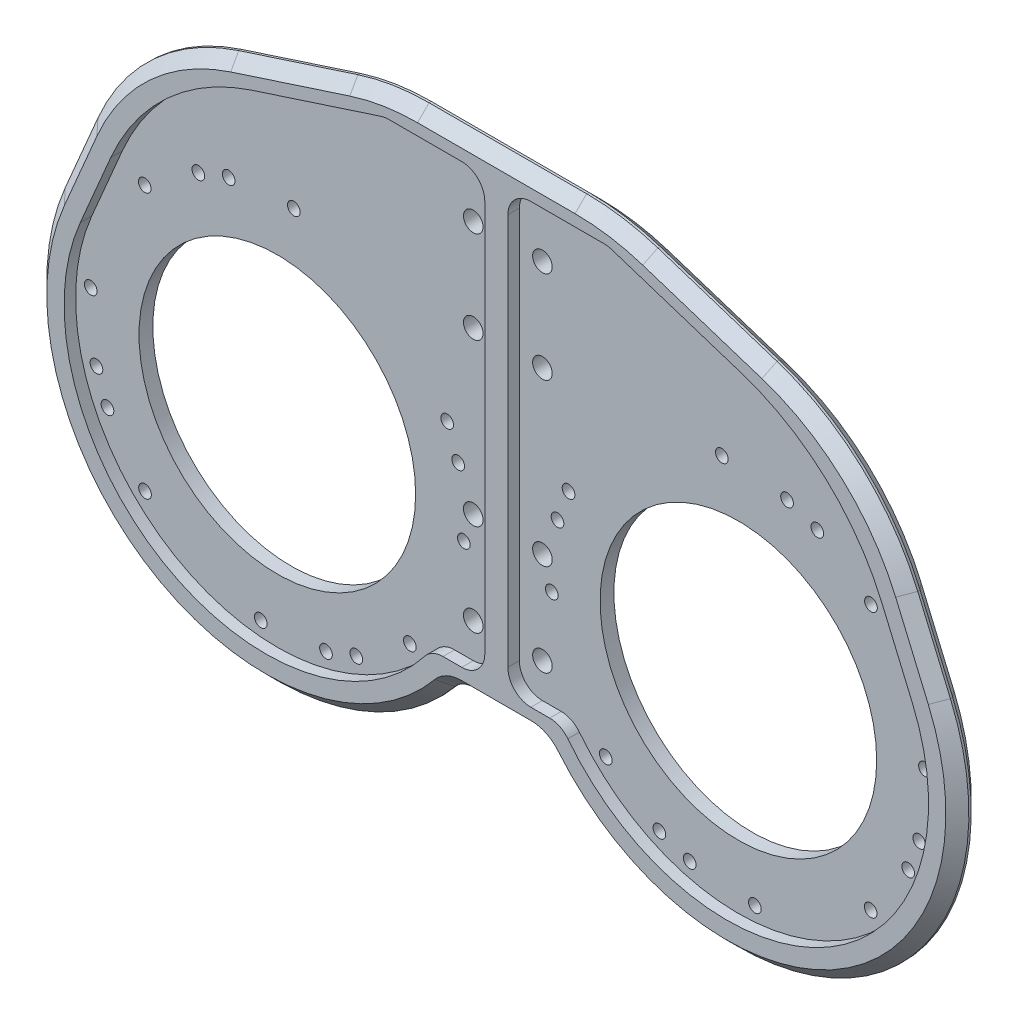
SolidWorks part; units mm, degrees
material "6061 合金"
ref_plane "前视基准面" through (0, 0, 0) normal (0, 0, 1) x (1, 0, 0)
ref_plane "上视基准面" through (0, 0, 0) normal (0, 1, 0) x (1, 0, 0)
ref_plane "右视基准面" through (0, 0, 0) normal (1, 0, 0) x (0, 0, -1)
other "Configuration Table"
sketch "草图1" plane through (0, 0, 0) normal (0, 0, 1) x (1, 0, 0)
  line L0 (0, 0) -> (0, 250) construction
  line L1 (0, 250) -> (769.4209, 0)
  line L3 (769.4209, 0) -> (0, 0)
  line L4 (-50, 352.899) -> (-50, -139.8009) construction
  line L5 (-869.4209, 0) -> (-100, 0)
  line L6 (-100, 250) -> (-869.4209, 0)
  line L7 (-100, 0) -> (-100, 250) construction
  line L8 (-100, 250) -> (0, 250)
  line L9 (0, 0) -> (-100, 0)
  circle A0 centre (50, 100) radius 85 construction
  circle A1 centre (50, 100) radius 60
  circle A2 centre (-150, 100) radius 85 construction
  circle A3 centre (-150, 100) radius 60
  dimension "D1" = 170
  dimension "D4" = 120
  dimension "D2" = 100
  dimension "D3" = 72
  dimension "D5" = 250
  dimension "D6" = 100
  dimension "D7" = 50
extrude "凸台-拉伸1" add sketch "草图1" along normal blind 6 contours L9 L3 L1 L8 L6 L5 A1 A3 region at (-50, 86.7466, 0)
sketch "草图4" plane through (0, 0, 6) normal (0, 0, 1) x (1, 0, 0)
  line L0 (-50, 330.4726) -> (-50, -61.6586) construction
  arc A0 (259.7806, 158.4465) -> (255.249, 156.3335) centre (257.5148, 157.39) ccw construction
  arc A1 (278.6673, 106.1128) -> (283.1989, 108.2258) centre (280.9331, 107.1693) ccw construction
  arc A2 (276.1928, 77.8292) -> (280.7244, 79.9423) centre (278.4586, 78.8857) ccw construction
  arc A3 (271.409, 64.6857) -> (275.9405, 66.7988) centre (273.6748, 65.7423) ccw construction
  arc A4 (255.1242, 41.4287) -> (259.6558, 43.5418) centre (257.39, 42.4852) ccw construction
  arc A5 (204.9035, 18.0104) -> (209.4351, 20.1235) centre (207.1693, 19.0669) ccw construction
  arc A6 (176.62, 20.4849) -> (181.1515, 22.598) centre (178.8857, 21.5414) ccw construction
  arc A7 (163.4765, 25.2687) -> (168.008, 27.3818) centre (165.7423, 26.3252) ccw construction
  arc A8 (140.2194, 41.5535) -> (144.751, 43.6665) centre (142.4852, 42.61) ccw construction
  arc A9 (121.3327, 93.8872) -> (116.8011, 91.7742) centre (119.0669, 92.8307) ccw construction
  arc A10 (123.8072, 122.1708) -> (119.2756, 120.0577) centre (121.5414, 121.1143) ccw construction
  arc A11 (128.591, 135.3143) -> (124.0595, 133.2012) centre (126.3252, 134.2577) ccw construction
  arc A12 (144.8758, 158.5713) -> (140.3442, 156.4582) centre (142.61, 157.5148) ccw construction
  arc A13 (195.0965, 181.9896) -> (190.5649, 179.8765) centre (192.8307, 180.9331) ccw construction
  arc A14 (223.38, 179.5151) -> (218.8485, 177.402) centre (221.1143, 178.4586) ccw construction
  arc A15 (236.5235, 174.7313) -> (231.992, 172.6182) centre (234.2577, 173.6748) ccw construction
  arc A16 (259.7806, 158.4465) -> (255.249, 156.3335) centre (257.5148, 157.39) ccw construction
  arc A17 (278.6673, 106.1128) -> (283.1989, 108.2258) centre (280.9331, 107.1693) ccw construction
  arc A18 (276.1928, 77.8292) -> (280.7244, 79.9423) centre (278.4586, 78.8857) ccw construction
  arc A19 (271.409, 64.6857) -> (275.9405, 66.7988) centre (273.6748, 65.7423) ccw construction
  arc A20 (255.1242, 41.4287) -> (259.6558, 43.5418) centre (257.39, 42.4852) ccw construction
  arc A21 (204.9035, 18.0104) -> (209.4351, 20.1235) centre (207.1693, 19.0669) ccw construction
  arc A22 (176.62, 20.4849) -> (181.1515, 22.598) centre (178.8857, 21.5414) ccw construction
  arc A23 (163.4765, 25.2687) -> (168.008, 27.3818) centre (165.7423, 26.3252) ccw construction
  arc A24 (140.2194, 41.5535) -> (144.751, 43.6665) centre (142.4852, 42.61) ccw construction
  arc A25 (121.3327, 93.8872) -> (116.8011, 91.7742) centre (119.0669, 92.8307) ccw construction
  arc A26 (123.8072, 122.1708) -> (119.2756, 120.0577) centre (121.5414, 121.1143) ccw construction
  arc A27 (128.591, 135.3143) -> (124.0595, 133.2012) centre (126.3252, 134.2577) ccw construction
  arc A28 (144.8758, 158.5713) -> (140.3442, 156.4582) centre (142.61, 157.5148) ccw construction
  arc A29 (195.0965, 181.9896) -> (190.5649, 179.8765) centre (192.8307, 180.9331) ccw construction
  arc A30 (223.38, 179.5151) -> (218.8485, 177.402) centre (221.1143, 178.4586) ccw construction
  arc A31 (236.5235, 174.7313) -> (231.992, 172.6182) centre (234.2577, 173.6748) ccw construction
  circle A32 centre (257.5148, 157.39) radius 2.75
  circle A33 centre (234.2577, 173.6748) radius 2.75
  circle A34 centre (221.1143, 178.4586) radius 2.75
  circle A35 centre (192.8307, 180.9331) radius 2.75
  circle A36 centre (142.61, 157.5148) radius 2.75
  circle A37 centre (126.3252, 134.2577) radius 2.75
  circle A38 centre (121.5414, 121.1143) radius 2.75
  circle A39 centre (119.0669, 92.8307) radius 2.75
  circle A40 centre (142.4852, 42.61) radius 2.75
  circle A41 centre (165.7423, 26.3252) radius 2.75
  circle A42 centre (178.8857, 21.5414) radius 2.75
  circle A43 centre (207.1693, 19.0669) radius 2.75
  circle A44 centre (257.39, 42.4852) radius 2.75
  circle A45 centre (273.6748, 65.7423) radius 2.75
  circle A46 centre (278.4586, 78.8857) radius 2.75
  circle A47 centre (280.9331, 107.1693) radius 2.75
  circle A48 centre (50, 100) radius 60 construction
  circle A49 centre (-150, 100) radius 60 construction
  arc A50 (-336.5235, 174.7313) -> (-331.992, 172.6182) centre (-334.2577, 173.6748) cw construction
  arc A51 (-323.38, 179.5151) -> (-318.8485, 177.402) centre (-321.1143, 178.4586) cw construction
  arc A52 (-295.0965, 181.9896) -> (-290.5649, 179.8765) centre (-292.8307, 180.9331) cw construction
  arc A53 (-244.8758, 158.5713) -> (-240.3442, 156.4582) centre (-242.61, 157.5148) cw construction
  arc A54 (-228.591, 135.3143) -> (-224.0595, 133.2012) centre (-226.3252, 134.2577) cw construction
  arc A55 (-223.8072, 122.1708) -> (-219.2756, 120.0577) centre (-221.5414, 121.1143) cw construction
  arc A56 (-221.3327, 93.8872) -> (-216.8011, 91.7742) centre (-219.0669, 92.8307) cw construction
  arc A57 (-240.2194, 41.5535) -> (-244.751, 43.6665) centre (-242.4852, 42.61) cw construction
  arc A58 (-263.4765, 25.2687) -> (-268.008, 27.3818) centre (-265.7423, 26.3252) cw construction
  arc A59 (-276.62, 20.4849) -> (-281.1515, 22.598) centre (-278.8857, 21.5414) cw construction
  arc A60 (-304.9035, 18.0104) -> (-309.4351, 20.1235) centre (-307.1693, 19.0669) cw construction
  arc A61 (-355.1242, 41.4287) -> (-359.6558, 43.5418) centre (-357.39, 42.4852) cw construction
  arc A62 (-371.409, 64.6857) -> (-375.9405, 66.7988) centre (-373.6748, 65.7423) cw construction
  arc A63 (-376.1928, 77.8292) -> (-380.7244, 79.9423) centre (-378.4586, 78.8857) cw construction
  arc A64 (-378.6673, 106.1128) -> (-383.1989, 108.2258) centre (-380.9331, 107.1693) cw construction
  arc A65 (-359.7806, 158.4465) -> (-355.249, 156.3335) centre (-357.5148, 157.39) cw construction
  circle A66 centre (-380.9331, 107.1693) radius 2.75
  circle A67 centre (-378.4586, 78.8857) radius 2.75
  circle A68 centre (-373.6748, 65.7423) radius 2.75
  circle A69 centre (-357.39, 42.4852) radius 2.75
  circle A70 centre (-307.1693, 19.0669) radius 2.75
  circle A71 centre (-278.8857, 21.5414) radius 2.75
  circle A72 centre (-265.7423, 26.3252) radius 2.75
  circle A73 centre (-242.4852, 42.61) radius 2.75
  circle A74 centre (-219.0669, 92.8307) radius 2.75
  circle A75 centre (-221.5414, 121.1143) radius 2.75
  circle A76 centre (-226.3252, 134.2577) radius 2.75
  circle A77 centre (-242.61, 157.5148) radius 2.75
  circle A78 centre (-292.8307, 180.9331) radius 2.75
  circle A79 centre (-321.1143, 178.4586) radius 2.75
  circle A80 centre (-334.2577, 173.6748) radius 2.75
  circle A81 centre (-357.5148, 157.39) radius 2.75
  dimension "D1" = 5.5
extrude "切除-拉伸2" [suppressed] cut sketch "草图4" against normal blind 10 contours A44 | A45 | A46 | A47 | A32 | A33 | A34 | A35 | A36 | A37 | A38 | A39 | A40 | A41 | A42 | A73 | A72 | A71 | A70 | A69 | A68 | A67 | A66 | A81 | A80 | A79 | A78 | A77 | A76 | A75 | A74 | A43
sketch "草图5" plane through (0, 0, 0) normal (0, 0, -1) x (-1, 0, 0)
  line L0 (50, 354.5789) -> (50, -118.9875) construction
  circle A16 centre (150, 100) radius 60 construction
  circle A17 centre (-50, 100) radius 60 construction
extrude "切除-拉伸3" [suppressed] cut sketch "草图5" against normal blind 5.5
fillet "圆角1" radius 100 2 edges at (-869.4209, 0, 3) (769.4209, 0, 3)
sketch "草图6" plane through (0, 0, 6) normal (0, 0, 1) x (1, 0, 0)
  line L0 (-50, 293.5967) -> (-50, -68.7433) construction
  line L1 (-70, 40) -> (-30, 40)
  line L2 (138.0457, 0) -> (-238.0457, 0) construction
  line L3 (50, 0) -> (-150, 0)
  circle A0 centre (50, 100) radius 85.25 construction
  arc A1 (-30, 40) -> (50, 0) centre (50, 100) ccw
  circle A2 centre (50, 100) radius 60 construction
  circle A3 centre (-150, 100) radius 60 construction
  arc A4 (-70, 40) -> (-150, 0) centre (-150, 100) cw
  dimension "D1" = 170.5
  dimension "D2" = 200
  dimension "D3" = 40
extrude "切除-拉伸4" cut sketch "草图6" against normal blind 10
sketch "草图7" plane through (0, 0, 6) normal (0, 0, 1) x (1, 0, 0)
  line L0 (-50, 316.0763) -> (-50, -100.7481) construction
  line L1 (-150, 0) -> (-238.0457, 0) construction
  line L2 (-241.9905, 139.2142) -> (-210, 214.2588)
  line L3 (-100, 250) -> (-268.9474, 195.1057) construction
  line L4 (-150, 0) -> (-238.0457, 0)
  line L5 (-210, 214.2588) -> (-268.9474, 195.1057)
  line L6 (110, 214.2588) -> (168.9474, 195.1057)
  line L7 (50, 0) -> (138.0457, 0)
  line L8 (141.9905, 139.2142) -> (110, 214.2588)
  arc A0 (-241.9905, 139.2142) -> (-150, 0) centre (-150, 100) ccw
  circle A1 centre (50, 100) radius 60 construction
  circle A2 centre (-150, 100) radius 60 construction
  arc A3 (-268.9474, 195.1057) -> (-238.0457, 0) centre (-238.0457, 100) ccw construction
  arc A4 (-268.9474, 195.1057) -> (-238.0457, 0) centre (-238.0457, 100) ccw
  arc A5 (168.9474, 195.1057) -> (138.0457, 0) centre (138.0457, 100) cw
  arc A6 (141.9905, 139.2142) -> (50, 0) centre (50, 100) cw
  dimension "D1" = 160
extrude "切除-拉伸5" cut sketch "草图7" against normal blind 83
fillet "圆角2" radius 10 2 edges at (-30, 40, 3) (-70, 40, 3)
fillet "圆角3" radius 100 4 edges at (110, 214.2588, 3) (0, 250, 3) (-100, 250, 3) (-210, 214.2588, 3)
sketch "草图8" plane through (0, 0, 6) normal (0, 0, 1) x (1, 0, 0)
  line L0 (-50, 283.5634) -> (-50, -10.7461) construction
  line L1 (-34.8528, 40) -> (-65.1472, 40) construction
  circle A0 centre (-150, 100) radius 60 construction
  circle A1 centre (50, 100) radius 60 construction
  circle A2 centre (-35, 65) radius 4.25
  circle A3 centre (-35, 105) radius 4.25
  circle A4 centre (-35, 175) radius 4.25
  circle A5 centre (-35, 215) radius 4.25
  circle A6 centre (-65, 215) radius 4.25
  circle A7 centre (-65, 175) radius 4.25
  circle A8 centre (-65, 105) radius 4.25
  circle A9 centre (-65, 65) radius 4.25
  dimension "D1" = 8.5
  dimension "D2" = 25
  dimension "D3" = 40
  dimension "D4" = 40
  dimension "D5" = 70
  dimension "D6" = 15
extrude "切除-拉伸6" cut sketch "草图8" against normal blind 10
sketch "草图9" plane through (0, 0, 6) normal (0, 0, 1) x (1, 0, 0)
  line L0 (-50, 299.1056) -> (-50, -13.7223) construction
  line L1 (-45, 50) -> (-21.807, 50)
  line L2 (-45, 240) -> (-1.5838, 240)
  line L3 (-1.5838, 240) -> (99.4298, 207.1787)
  line L4 (99.4298, 207.1787) -> (130.4916, 134.3125)
  line L5 (-34.8528, 40) -> (-65.1472, 40) construction
  line L6 (-84.1616, 250) -> (-15.8384, 250) construction
  line L7 (15.0633, 245.1057) -> (66.7459, 228.3129) construction
  line L8 (127.8347, 172.4215) -> (141.9905, 139.2142) construction
  line L9 (-45, 240) -> (-45, 50)
  line L10 (-55, 240) -> (-55, 50)
  line L11 (-199.4298, 207.1787) -> (-230.4916, 134.3125)
  line L12 (-98.4162, 240) -> (-199.4298, 207.1787)
  line L13 (-55, 240) -> (-98.4162, 240)
  line L14 (-55, 50) -> (-78.193, 50)
  line L21 (141.9905, 139.2142) -> (127.8347, 172.4215)
  line L22 (66.7459, 228.3129) -> (15.0633, 245.1057)
  line L23 (-15.8384, 250) -> (-84.1616, 250)
  line L24 (-115.0633, 245.1057) -> (-166.7459, 228.3129)
  line L25 (-227.8347, 172.4215) -> (-241.9905, 139.2142)
  line L26 (-65.1472, 40) -> (-34.8528, 40)
  line L27 (141.9905, 139.2142) -> (127.8347, 172.4215)
  line L28 (66.7459, 228.3129) -> (15.0633, 245.1057)
  line L29 (-15.8384, 250) -> (-84.1616, 250)
  line L30 (-115.0633, 245.1057) -> (-166.7459, 228.3129)
  line L31 (-227.8347, 172.4215) -> (-241.9905, 139.2142)
  line L32 (-65.1472, 40) -> (-34.8528, 40)
  circle A0 centre (50, 100) radius 87.5 construction
  circle A1 centre (50, 100) radius 60 construction
  circle A2 centre (-150, 100) radius 60 construction
  arc A3 (-21.807, 50) -> (130.4916, 134.3125) centre (50, 100) ccw
  circle A4 centre (-150, 100) radius 87.5 construction
  arc A5 (-78.193, 50) -> (-230.4916, 134.3125) centre (-150, 100) cw
  arc A14 (127.8347, 172.4215) -> (66.7459, 228.3129) centre (35.8442, 133.2073) ccw
  arc A15 (15.0633, 245.1057) -> (-15.8384, 250) centre (-15.8384, 150) ccw
  arc A16 (-84.1616, 250) -> (-115.0633, 245.1057) centre (-84.1616, 150) ccw
  arc A17 (-166.7459, 228.3129) -> (-227.8347, 172.4215) centre (-135.8442, 133.2073) ccw
  arc A18 (-241.9905, 139.2142) -> (-72.8611, 36.3636) centre (-150, 100) ccw
  arc A19 (-65.1472, 40) -> (-72.8611, 36.3636) centre (-65.1472, 30) ccw
  arc A20 (-27.1389, 36.3636) -> (-34.8528, 40) centre (-34.8528, 30) ccw
  arc A21 (-27.1389, 36.3636) -> (141.9905, 139.2142) centre (50, 100) ccw
  arc A22 (127.8347, 172.4215) -> (66.7459, 228.3129) centre (35.8442, 133.2073) ccw
  arc A23 (15.0633, 245.1057) -> (-15.8384, 250) centre (-15.8384, 150) ccw
  arc A24 (-84.1616, 250) -> (-115.0633, 245.1057) centre (-84.1616, 150) ccw
  arc A25 (-166.7459, 228.3129) -> (-227.8347, 172.4215) centre (-135.8442, 133.2073) ccw
  arc A26 (-241.9905, 139.2142) -> (-72.8611, 36.3636) centre (-150, 100) ccw
  arc A27 (-65.1472, 40) -> (-72.8611, 36.3636) centre (-65.1472, 30) ccw
  arc A28 (-27.1389, 36.3636) -> (-34.8528, 40) centre (-34.8528, 30) ccw
  arc A29 (-27.1389, 36.3636) -> (141.9905, 139.2142) centre (50, 100) ccw
  dimension "D1" = 175
  dimension "D2" = 10
  dimension "D3" = 10
  dimension "D4" = 10
  dimension "D5" = 5
  dimension "D6" = 0
extrude "凸台-拉伸2" add sketch "草图9" along normal blind 5
sketch "草图10" plane through (0, 0, 6) normal (0, 0, 1) x (1, 0, 0)
  line L0 (-20, 230) -> (-20, 130)
  line L1 (-20, 130) -> (66.6025, 180)
  line L2 (66.6025, 180) -> (-20, 230)
  line L3 (-50, 285.8782) -> (-50, -42.8226) construction
  line L4 (-15.8384, 250) -> (-84.1616, 250) construction
  line L5 (-166.6025, 180) -> (-80, 230)
  line L6 (-80, 130) -> (-166.6025, 180)
  line L7 (-80, 230) -> (-80, 130)
  circle A0 centre (50, 100) radius 60 construction
  circle A1 centre (-150, 100) radius 60 construction
  dimension "D1" = 30
  dimension "D2" = 20
  dimension "D3" = 100
  dimension "D4" = 100
  dimension "D5" = 100
extrude "切除-拉伸7" [suppressed] cut sketch "草图10" against normal blind 94
fillet "圆角4" [suppressed] radius 10
chamfer "倒角1" [suppressed] distance 5 angle 45
sketch "草图15" plane through (0, 0, 6) normal (0, 0, 1) x (1, 0, 0)
  line L0 (50, 100) -> (41.8993, 191.4878) construction
  line L1 (50, 100) -> (78.1821, 204.738) construction
  line L2 (50, 100) -> (95.9488, 198.8075) construction
  line L3 (50, 100) -> (126.3654, 176.2056) construction
  line L4 (-45, 240) -> (-45, 50) construction
  line L5 (-50, 286.5396) -> (-50, -57.042) construction
  line L6 (-150, 100) -> (-226.3654, 176.2056) construction
  line L7 (-150, 100) -> (-195.9488, 198.8075) construction
  line L8 (-150, 100) -> (-178.1821, 204.738) construction
  line L9 (-150, 100) -> (-141.8993, 191.4878) construction
  circle A0 centre (42.8338, 180.9334) radius 2.75
  circle A1 centre (71.1112, 178.4594) radius 2.75
  circle A2 centre (84.2606, 173.6734) radius 2.75
  circle A3 centre (107.5126, 157.3922) radius 2.75
  circle A4 centre (107.3922, 42.4874) radius 2.75
  circle A5 centre (123.6734, 65.7394) radius 2.75
  circle A6 centre (128.4594, 78.8888) radius 2.75
  circle A7 centre (130.9334, 107.1662) radius 2.75
  circle A8 centre (-7.5126, 42.6078) radius 2.75
  circle A9 centre (15.7394, 26.3266) radius 2.75
  circle A10 centre (28.8888, 21.5406) radius 2.75
  circle A11 centre (57.1662, 19.0666) radius 2.75
  circle A12 centre (-7.3922, 157.5126) radius 2.75 construction
  circle A13 centre (-23.6734, 134.2606) radius 2.75
  circle A14 centre (-28.4594, 121.1112) radius 2.75
  circle A15 centre (-30.9334, 92.8338) radius 2.75
  circle A16 centre (50, 100) radius 60 construction
  circle A17 centre (-150, 100) radius 60 construction
  circle A18 centre (-69.0666, 92.8338) radius 2.75
  circle A19 centre (-71.5406, 121.1112) radius 2.75
  circle A20 centre (-76.3266, 134.2606) radius 2.75
  circle A21 centre (-92.6078, 157.5126) radius 2.75 construction
  circle A22 centre (-157.1662, 19.0666) radius 2.75
  circle A23 centre (-128.8888, 21.5406) radius 2.75
  circle A24 centre (-115.7394, 26.3266) radius 2.75
  circle A25 centre (-92.4874, 42.6078) radius 2.75
  circle A26 centre (-230.9334, 107.1662) radius 2.75
  circle A27 centre (-228.4594, 78.8888) radius 2.75
  circle A28 centre (-223.6734, 65.7394) radius 2.75
  circle A29 centre (-207.3922, 42.4874) radius 2.75
  circle A30 centre (-207.5126, 157.3922) radius 2.75
  circle A31 centre (-184.2606, 173.6734) radius 2.75
  circle A32 centre (-171.1112, 178.4594) radius 2.75
  circle A33 centre (-142.8338, 180.9334) radius 2.75
  point P43 (50, 100)
  point P84 (-150, 100)
  point P85 (50, 100)
  dimension "D9" = 5.5
  dimension "D1" = 5.06
  dimension "D2" = 30
  dimension "D3" = 30
  dimension "D4" = 50.12
  dimension "D5" = 81.25
  dimension "D6" = 81.25
  dimension "D7" = 81.25
  dimension "D8" = 81.25
  dimension "D10" = 4
extrude "切除-拉伸8" cut sketch "草图15" against normal blind 48.5
sketch "草图16" plane through (0, 0, 0) normal (0, 0, -1) x (-1, 0, 0)
  line L0 (50, 280.5872) -> (50, -6.4472) construction
  circle A0 centre (150, 100) radius 60 construction
  circle A1 centre (-50, 100) radius 60 construction
  circle A2 centre (142.8338, 180.9334) radius 6
  circle A3 centre (171.1112, 178.4594) radius 6
  circle A4 centre (184.2606, 173.6734) radius 6
  circle A5 centre (207.5126, 157.3922) radius 6
  circle A6 centre (230.9334, 107.1662) radius 6
  circle A7 centre (228.4594, 78.8888) radius 6
  circle A8 centre (223.6734, 65.7394) radius 6
  circle A9 centre (207.3922, 42.4874) radius 6
  circle A10 centre (157.1662, 19.0666) radius 6
  circle A11 centre (128.8888, 21.5406) radius 6
  circle A12 centre (115.7394, 26.3266) radius 6
  circle A13 centre (92.4874, 42.6078) radius 6
  circle A14 centre (69.0666, 92.8338) radius 6
  circle A15 centre (71.5406, 121.1112) radius 6
  circle A16 centre (76.3266, 134.2606) radius 6
  circle A19 centre (23.6734, 134.2606) radius 6
  circle A20 centre (28.4594, 121.1112) radius 6
  circle A21 centre (30.9334, 92.8338) radius 6
  circle A22 centre (7.5126, 42.6078) radius 6
  circle A23 centre (-15.7394, 26.3266) radius 6
  circle A24 centre (-28.8888, 21.5406) radius 6
  circle A25 centre (-57.1662, 19.0666) radius 6
  circle A26 centre (-107.3922, 42.4874) radius 6
  circle A27 centre (-123.6734, 65.7394) radius 6
  circle A28 centre (-128.4594, 78.8888) radius 6
  circle A29 centre (-130.9334, 107.1662) radius 6
  circle A30 centre (-107.5126, 157.3922) radius 6
  circle A31 centre (-84.2606, 173.6734) radius 6
  circle A32 centre (-71.1112, 178.4594) radius 6
  circle A33 centre (-42.8338, 180.9334) radius 6
  dimension "D1" = 12
extrude "切除-拉伸10" [suppressed] cut sketch "草图16" against normal blind 5.5
fillet "圆角5" radius 10 8 edges at (-78.193, 50, 8.5) (-55, 50, 8.5) (-45, 50, 8.5) (-21.807, 50, 8.5) (-1.5838, 240, 8.5) (-45, 240, 8.5) (-55, 240, 8.5) (-98.4162, 240, 8.5)
fillet "圆角6" radius 100 2 edges at (-199.4298, 207.1787, 8.5) (99.4298, 207.1787, 8.5)
chamfer "倒角2" distance 5 angle 45 28 edges at (134.9126, 155.8179, 11) (103.3467, 206.9868, 11) (101.9587, 14.5582, 11) (40.9046, 236.7093, 11) (-30.5888, 39.0453, 11) (-0.195, 248.7688, 11) (-50, 40, 11) (-50, 250, 11) (-69.4112, 39.0453, 11) (-99.805, 248.7688, 11) (-201.9587, 14.5582, 11) (-140.9046, 236.7093, 11) (-234.9126, 155.8179, 11) (-203.3467, 206.9868, 11) (134.9126, 155.8179, 0) (101.9587, 14.5582, 0) (103.3467, 206.9868, 0) (-30.5888, 39.0453, 0) (40.9046, 236.7093, 0) (-50, 40, 0) (-0.195, 248.7688, 0) (-69.4112, 39.0453, 0) (-50, 250, 0) (-201.9587, 14.5582, 0) (-99.805, 248.7688, 0) (-234.9126, 155.8179, 0) (-140.9046, 236.7093, 0) (-203.3467, 206.9868, 0)
